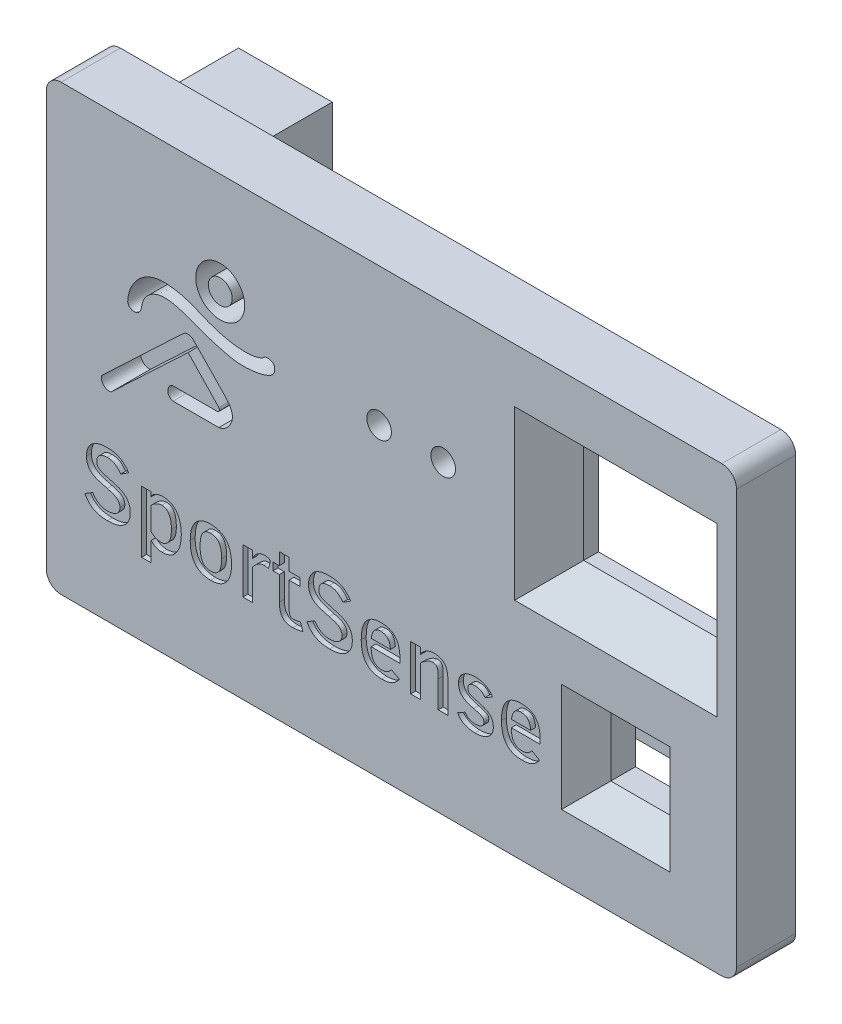
SolidWorks part; units mm, degrees
note: The reader was unsure of these and kept them because the rebuilt part matched: shared geometry of "Schizzo1<5>", "Schizzo1<6>".
ref_plane "Piano frontale" through (0, 0, 0) normal (0, 0, 1) x (1, 0, 0)
ref_plane "Piano superiore" through (0, 0, 0) normal (0, 1, 0) x (1, 0, 0)
ref_plane "Piano destro" through (0, 0, 0) normal (1, 0, 0) x (0, 0, -1)
sketch "Schizzo1" plane through (0, 0, 0) normal (0, 0, 1) x (1, 0, 0)
  line L0 (35.1474, 25.4062) -> (35.1474, 5.4062)
  line L1 (-63.8526, 43.4062) -> (70.1474, 43.4062)
  line L2 (-66.8526, 40.4062) -> (-66.8526, -43.5938)
  line L3 (-63.8526, -46.5938) -> (70.1474, -46.5938)
  line L4 (73.1474, 40.4062) -> (73.1474, -43.5938)
  line L5 (35.1474, 5.4062) -> (62.1474, 5.4062)
  line L6 (62.1474, 5.4062) -> (62.1474, 25.4062)
  line L7 (62.1474, 25.4062) -> (35.1474, 25.4062)
  line L9 (42.6474, -16.5938) -> (54.6474, -16.5938)
  line L10 (42.6474, -16.5938) -> (42.6474, -28.5938)
  line L11 (42.6474, -28.5938) -> (54.6474, -28.5938)
  line L12 (54.6474, -16.5938) -> (54.6474, -28.5938)
  line L20 (-60.8526, 40.4062) -> (67.1474, 40.4062)
  line L21 (70.1474, 37.4062) -> (70.1474, -40.5938)
  line L22 (67.1474, -43.5938) -> (-60.8526, -43.5938)
  line L23 (-63.8526, -40.5938) -> (-63.8526, 37.4062)
  line L24 (59.1414, 281.4902) -> (400.4747, 281.4902) construction
  line L25 (-55.8526, 25.4062) -> (-20.8526, 25.4062) construction
  line L27 (-20.8526, 25.4062) -> (-20.8526, -9.5938) construction
  line L28 (-20.8526, -9.5938) -> (-55.8526, -9.5938) construction
  line L29 (-55.8526, -9.5938) -> (-55.8526, 25.4062) construction
  line L30 (-55.8526, -9.5938) -> (-55.8526, -35.7434) construction
  line L31 (42.6474, -28.5938) -> (-55.8526, -28.5938) construction
  line L36 (-63.8526, 37.4062) -> (-60.8526, 37.4062)
  line L37 (-60.8526, 37.4062) -> (-60.8526, 40.4062)
  line L38 (67.1474, 40.4062) -> (67.1474, 37.4062)
  line L39 (67.1474, 37.4062) -> (70.1474, 37.4062)
  line L40 (67.1474, -43.5938) -> (67.1474, -40.5938)
  line L41 (67.1474, -40.5938) -> (70.1474, -40.5938)
  line L42 (-63.8526, -40.5938) -> (-60.8526, -40.5938)
  line L43 (-60.8526, -40.5938) -> (-60.8526, -43.5938)
  line L44 (-37.0106, 11.5538) -> (-30.3742, 4.6628)
  line L46 (-31.8517, -1.2651) -> (-41.162, -1.2651)
  line L48 (-41.2786, 1.4114) -> (-32.2136, 1.4114)
  line L49 (-31.8517, 2.2564) -> (-38.091, 8.8032)
  line L50 (-38.091, 8.8032) -> (-53.7041, -5.9378)
  line L52 (-55.632, -4.006) -> (-39.1215, 11.6033)
  circle A0 centre (13.6474, 15.4062) radius 2.5
  circle A1 centre (0.6474, 15.4062) radius 2.5
  arc A2 (-66.8526, 40.4062) -> (-63.8526, 43.4062) centre (-63.8526, 40.4062) cw
  arc A3 (70.1474, 43.4062) -> (73.1474, 40.4062) centre (70.1474, 40.4062) cw
  arc A4 (73.1474, -43.5938) -> (70.1474, -46.5938) centre (70.1474, -43.5938) cw
  arc A5 (-66.8526, -43.5938) -> (-63.8526, -46.5938) centre (-63.8526, -43.5938) ccw
  circle A10 centre (-31.5731, 22.7571) radius 4.9713
  circle A11 centre (-31.5731, 22.7571) radius 2.4232
  arc A12 (-37.0106, 11.5538) -> (-39.1215, 11.6033) centre (-38.091, 10.5133) ccw
  arc A14 (-32.2136, 1.4114) -> (-31.8517, 2.2564) centre (-32.2136, 1.9114) ccw
  spline S0 degree 3 poles (-55.632, -4.006) (-55.9591, -5.0791) (-54.7823, -6.3071) (-53.7041, -5.9378) knots 0 0 0 0 1 1 1 1
  spline S1 degree 3 poles (-41.2786, 1.4114) (-41.6647, 1.2741) (-42.1748, 0.7702) (-42.1312, 0.0504) (-42.1973, -0.4178) (-41.8223, -0.925) (-41.4979, -1.3049) (-41.162, -1.2651) knots 0 0 0 0 0.363254 0.491066 0.604087 0.746087 1 1 1 1
  spline S2 degree 3 poles (-50.1552, 11.0521) (-49.7266, 10.6313) (-49.0806, 10.4614) (-48.2227, 10.5839) (-47.5391, 11.5566) (-47.4543, 12.9484) (-46.6929, 14.4156) (-45.4919, 15.4017) (-44.1737, 15.9629) (-42.4967, 16.1372) (-40.3702, 15.7772) (-37.9911, 14.9917) (-34.9985, 13.7349) (-31.8144, 12.8261) (-28.2268, 11.9233) (-25.176, 12.0076) (-22.597, 12.5341) (-20.627, 13.3926) (-20.5038, 14.6676) (-20.6279, 15.4085) (-21.2217, 15.8308) (-21.8899, 15.9566) (-22.5331, 15.8347) (-23.0042, 15.3545) (-23.8979, 14.9957) (-25.0107, 14.7619) (-26.283, 14.6648) (-29.4061, 14.7517) (-33.2911, 15.7891) (-37.7954, 17.9421) (-41.149, 18.6948) (-44.4005, 18.7665) (-47.0344, 17.8135) (-49.4341, 15.4195) (-50.3042, 13.0748) (-50.3395, 11.4354) (-50.1552, 11.0521) (-49.7266, 10.6313) (-49.0806, 10.4614) knots -0.017038 -0.01547 -0.00674 0 0.0098 0.020745 0.034916 0.056066 0.080028 0.103061 0.12129 0.140595 0.174332 0.212673 0.247713 0.313116 0.354081 0.405938 0.43994 0.471764 0.483395 0.492165 0.502628 0.51184 0.521126 0.529102 0.539884 0.561685 0.577685 0.59435 0.695262 0.746002 0.808029 0.840487 0.884323 0.923245 0.982962 0.98453 0.99326 1 1.0098 1.020745 1.034916 only from (-49.7606, 10.711) to (-49.7606, 10.711)
  spline S3 degree 3 poles (-31.8517, -1.2651) (-31.4427, -1.1773) (-30.6335, -0.9022) (-29.4808, 0.2799) (-28.9019, 1.8119) (-29.3138, 3.0503) (-29.6593, 3.8737) (-30.1565, 4.3267) (-30.3742, 4.6628) knots 0 0 0 0 0.167537 0.327367 0.648773 0.740515 0.840902 1 1 1 1
  point P18 (-66.8526, 43.4062)
  point P21 (73.1474, 43.4062)
  point P24 (73.1474, -46.5938)
  point P29 (35.1474, 15.4062)
  point P40 (48.6474, -16.5938)
  point P42 (48.6474, 5.4062)
  dimension "D5" = 5
  dimension "D6" = 3
  dimension "D7" = 15
  dimension "D8" = 8
  dimension "D9" = 21.5
  dimension "D10" = 13
  dimension "D11" = 22
  dimension "D12" = 12
  dimension "D13" = 8
  dimension "D14" = 35
  dimension "D1" = 140
  dimension "D2" = 90
  dimension "D3" = 27
  dimension "D4" = 20
extrude "Bordo" add sketch "Schizzo1" against normal blind 2
extrude "Coperchio" add sketch "Schizzo1<5>" along normal blind 10
sketch "Schizzo1<5>" plane through (0, 0, 0) normal (0, 0, 1) x (1, 0, 0) same geometry as "Schizzo1"
extrude "Logo" add sketch "Schizzo1<6>" along normal blind 2 contours A10 A11 | S2 | L46 S3 L44 A12 L52 S0 L50 L49 A14 L48 S1
sketch "Schizzo1<6>" plane through (0, 0, 0) normal (0, 0, 1) x (1, 0, 0) same geometry as "Schizzo1"
sketch "Schizzo2" plane through (0, 0, 10) normal (0, 0, 1) x (1, 0, 0)
  line L0 (42.6474, -28.5938) -> (-59.8526, -28.5938) construction
  line L1 (-59.8526, -28.5938) -> (-59.8526, -11.8108) construction
  line L2 (-66.8526, 40.4062) -> (-66.8526, -43.5938) construction
  text T0 "<b>SportSense</b>\r\n" font "Clear Sans" height 12
  dimension "D1" = 7
extrude "Nome" cut sketch "Schizzo2" against normal blind 1
sketch "Schizzo4" plane through (0, 0, 0) normal (0, 0, -1) x (-1, 0, 0)
  line L4 (-61.1474, -1.5938) -> (-36.1474, -1.5938) construction
  line L5 (-34.1474, 0.4062) -> (-34.1474, 27.4062) construction
  line L6 (-36.1474, 29.4062) -> (-61.1474, 29.4062) construction
  line L7 (-63.1474, 27.4062) -> (-63.1474, 0.4062) construction
  line L8 (-62.1474, 25.4062) -> (-35.1474, 25.4062) construction
  line L9 (-62.1474, 25.4062) -> (-35.1474, 25.4062) construction
  line L10 (-62.1474, 5.4062) -> (-62.1474, 25.4062) construction
  line L13 (-35.1474, 5.4062) -> (-62.1474, 5.4062) construction
  line L14 (-17.9418, 2.3389) -> (-17.9418, -11.6611) construction
  line L15 (-15.9418, -13.6611) -> (5.0582, -13.6611) construction
  line L16 (7.0582, -11.6611) -> (7.0582, 2.3389) construction
  line L17 (5.0582, 4.3389) -> (-15.9418, 4.3389) construction
  arc A0 (-61.1474, 29.4062) -> (-63.1474, 27.4062) centre (-61.1474, 27.4062) ccw construction
  arc A1 (-61.1474, -1.5938) -> (-63.1474, 0.4062) centre (-61.1474, 0.4062) cw construction
  arc A2 (-36.1474, -1.5938) -> (-34.1474, 0.4062) centre (-36.1474, 0.4062) ccw construction
  arc A3 (-34.1474, 27.4062) -> (-36.1474, 29.4062) centre (-36.1474, 27.4062) ccw construction
  circle A4 centre (-36.1474, 27.4062) radius 1
  circle A5 centre (-61.1474, 27.4062) radius 1
  circle A6 centre (-36.1474, 0.4062) radius 1
  circle A7 centre (-61.1474, 0.4062) radius 1
  arc A8 (-17.9418, -11.6611) -> (-15.9418, -13.6611) centre (-15.9418, -11.6611) ccw construction
  arc A9 (7.0582, -11.6611) -> (5.0582, -13.6611) centre (5.0582, -11.6611) cw construction
  arc A10 (7.0582, 2.3389) -> (5.0582, 4.3389) centre (5.0582, 2.3389) ccw construction
  arc A11 (-15.9418, 4.3389) -> (-17.9418, 2.3389) centre (-15.9418, 2.3389) ccw construction
  circle A12 centre (-15.9418, 2.3389) radius 1
  circle A13 centre (5.0582, 2.3389) radius 1
  circle A14 centre (5.0582, -11.6611) radius 1
  circle A15 centre (-15.9418, -11.6611) radius 1
  point P6 (-48.6474, 25.4062)
  point P7 (-48.6474, 29.4062)
  point P30 (-17.9418, -13.6611)
  point P35 (7.0582, 4.3389)
  point P38 (-17.9418, 4.3389)
  dimension "D2" = 2
  dimension "D3" = 2
  dimension "D4" = 5
  dimension "D1" = 1
  dimension "D5" = 18
  dimension "D6" = 25
sketch "Schizzo5" plane through (0, 0, 0) normal (0, 0, -1) x (-1, 0, 0)
  line L0 (54.8526, 40.4062) -> (54.8526, 12.4062)
  line L1 (60.8526, 40.4062) -> (-67.1474, 40.4062) construction
  line L2 (54.8526, 12.4062) -> (35.8526, 12.4062)
  line L3 (35.8526, 12.4062) -> (35.8526, 40.4062)
  line L4 (35.8526, 40.4062) -> (54.8526, 40.4062)
  line L5 (63.8526, -40.5938) -> (63.8526, 37.4062) construction
  dimension "D1" = 9
  dimension "D2" = 19
  dimension "D3" = 28
extrude "Fermo Batteria" add sketch "Schizzo5" along normal blind 17
chamfer "Smusso3" distance 7 angle 45 4 edges at (62.1474, 15.4062, 10) (48.6474, 5.4062, 10) (35.1474, 15.4062, 10) (48.6474, 25.4062, 10)
chamfer "Smusso4" distance 5 angle 45 4 edges at (42.6474, -22.5938, 10) (48.6474, -28.5938, 10) (54.6474, -22.5938, 10) (48.6474, -16.5938, 10)
sketch "Schizzo7" plane through (0, 0, 0) normal (0, 0, -1) x (-1, 0, 0)
  line L0 (-42.6474, -23.5938) -> (-40.6474, -23.5938)
  line L1 (-42.6474, -16.5938) -> (-42.6474, -28.5938) construction
  line L2 (-40.6474, -23.5938) -> (-40.6474, -21.5938)
  line L3 (-40.6474, -21.5938) -> (-42.6474, -21.5938)
  line L4 (-42.6474, -21.5938) -> (-42.6474, -23.5938)
  line L5 (-54.6474, -23.5938) -> (-56.6474, -23.5938)
  line L6 (-54.6474, -16.5938) -> (-54.6474, -28.5938) construction
  line L7 (-56.6474, -23.5938) -> (-56.6474, -21.5938)
  line L8 (-56.6474, -21.5938) -> (-54.6474, -21.5938)
  line L9 (-54.6474, -21.5938) -> (-54.6474, -23.5938)
  line L10 (-54.6474, -16.5938) -> (-54.6474, -28.5938)
  point P14 (-54.6474, -22.5938)
  point P15 (-54.6474, -22.5938)
  point P16 (-42.6474, -22.5938)
  line M6 (-42.6474, -16.5938) -> (-42.6474, -28.5938)
  line M8 (-54.6474, -28.5938) -> (-54.6474, -16.5938)
  dimension "D1" = 2
  dimension "D2" = 2
extrude "Aggancio Tasto 1" add sketch "Schizzo7" along normal blind 2 contours L8 L7 L5 M8 | L2 L3 L0 M6
sketch "Schizzo8" plane through (54.6474, 0, 0) normal (-1, 0, 0) x (0, 0, 1)
  line L0 (-2, -21.5938) -> (-2, -23.5938)
  line L2 (0, -23.5938) -> (0, -21.5938)
  line L3 (0, -21.5938) -> (-2, -21.5938)
  line L4 (-2, -23.5938) -> (-2, -21.5938) construction
  line L5 (-2, -23.5938) -> (0, -23.5938)
extrude "Aggancio Tasto 2" add sketch "Schizzo8" along normal up to surface (12 mm away) up to face at (42.6474, -22.5938, 0.75)
chamfer "Smusso5" distance 2 angle 45 2 edges at (56.6474, -22.5938, -2) (40.6474, -22.5938, -2)
